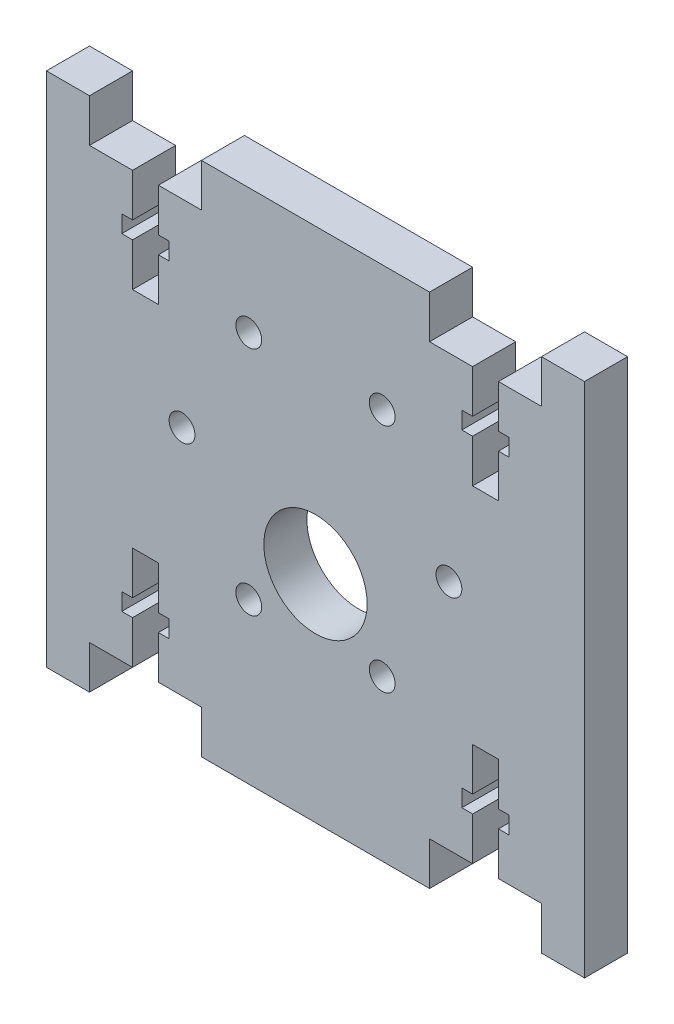
SolidWorks part; units mm, degrees
ref_plane "Front Plane" through (0, 0, 0) normal (0, 0, 1) x (1, 0, 0)
ref_plane "Top Plane" through (0, 0, 0) normal (0, 1, 0) x (1, 0, 0)
ref_plane "Right Plane" through (0, 0, 0) normal (1, 0, 0) x (0, 0, -1)
sketch "Sketch1" plane through (0, 0, 0) normal (0, 0, 1) x (1, 0, 0)
  line L1 (-27.5, -27) -> (27.5, -27)
  line L2 (-27.5, -27) -> (-27.5, 23)
  line L3 (-27.5, 23) -> (27.5, 23)
  line L4 (27.5, -27) -> (27.5, 23)
  line L5 (-27.5, -7) -> (27.5, -7) construction
  circle A2 centre (0, -7) radius 6
  circle A3 centre (0, 0) radius 15.5 construction
  circle A4 centre (-15.5, 0) radius 1.5
  circle A5 centre (-7.75, 13.4234) radius 1.5
  circle A6 centre (7.75, 13.4234) radius 1.5
  circle A7 centre (15.5, 0) radius 1.5
  circle A8 centre (7.75, -13.4234) radius 1.5
  circle A9 centre (-7.75, -13.4234) radius 1.5
  dimension "D1" = 12
  dimension "D5" = 3
  dimension "D8" = 31
  dimension "D2" = 55
  dimension "D3" = 50
  dimension "D6" = 20
  dimension "D7" = 7
  dimension "D4" = 6
extrude "Boss-Extrude1" add sketch "Sketch1" along normal blind 5
sketch "Sketch2" plane through (0, 0, 5) normal (0, 0, 1) x (1, 0, 0)
  line L0 (-27.5, -27) -> (27.5, -27) construction
  line L1 (-22.5, -20) -> (-17, -20)
  line L2 (-22.5, -20) -> (-22.5, -22)
  line L3 (-22.5, -22) -> (-17, -22)
  line L4 (-17, -20) -> (-17, -22)
  line L5 (-22.5, -20) -> (-17, -22) construction
  line L6 (-22.5, -22) -> (-17, -20) construction
  line L7 (17, -20) -> (22.5, -20)
  line L8 (17, -20) -> (17, -22)
  line L9 (17, -22) -> (22.5, -22)
  line L10 (22.5, -20) -> (22.5, -22)
  line L11 (17, -20) -> (22.5, -22) construction
  line L12 (17, -22) -> (22.5, -20) construction
  line L13 (-18.25, -15) -> (-21.25, -15)
  line L14 (-18.25, -15) -> (-18.25, -27)
  line L15 (-18.25, -27) -> (-21.25, -27)
  line L16 (-21.25, -15) -> (-21.25, -27)
  line L17 (-18.25, -15) -> (-21.25, -27) construction
  line L18 (-18.25, -27) -> (-21.25, -15) construction
  line L19 (-27.5, -2) -> (27.5, -2) construction
  line L20 (21.25, -15) -> (18.25, -15)
  line L21 (21.25, -15) -> (21.25, -27)
  line L22 (21.25, -27) -> (18.25, -27)
  line L23 (18.25, -15) -> (18.25, -27)
  line L24 (21.25, -15) -> (18.25, -27) construction
  line L25 (21.25, -27) -> (18.25, -15) construction
  line L26 (-27.5, 23) -> (-27.5, -27) construction
  line L27 (27.5, -27) -> (27.5, 23) construction
  line L28 (21.25, 23) -> (18.25, 11) construction
  line L29 (21.25, 11) -> (18.25, 23) construction
  line L30 (-18.25, 23) -> (-21.25, 11) construction
  line L31 (-18.25, 11) -> (-21.25, 23) construction
  line L32 (17, 18) -> (22.5, 16) construction
  line L33 (17, 16) -> (22.5, 18) construction
  line L34 (-22.5, 18) -> (-17, 16) construction
  line L35 (-22.5, 16) -> (-17, 18) construction
  line L36 (18.25, 11) -> (18.25, 23)
  line L37 (21.25, 23) -> (18.25, 23)
  line L38 (21.25, 11) -> (21.25, 23)
  line L39 (21.25, 11) -> (18.25, 11)
  line L40 (-21.25, 11) -> (-21.25, 23)
  line L41 (-18.25, 23) -> (-21.25, 23)
  line L42 (-18.25, 11) -> (-18.25, 23)
  line L43 (-18.25, 11) -> (-21.25, 11)
  line L44 (22.5, 16) -> (22.5, 18)
  line L45 (17, 18) -> (22.5, 18)
  line L46 (17, 16) -> (17, 18)
  line L47 (17, 16) -> (22.5, 16)
  line L48 (-17, 16) -> (-17, 18)
  line L49 (-22.5, 18) -> (-17, 18)
  line L50 (-22.5, 16) -> (-22.5, 18)
  line L51 (-22.5, 16) -> (-17, 16)
  point P0 (-19.75, -21)
  point P5 (19.75, -21)
  point P10 (-19.75, -21)
  point P17 (19.75, -21)
  point P44 (19.75, 17)
  point P45 (-19.75, 17)
  dimension "D1" = 5.5
  dimension "D2" = 2
  dimension "D3" = 5.5
  dimension "D4" = 2
  dimension "D5" = 3
  dimension "D6" = 3
  dimension "D7" = 12
  dimension "D8" = 12
  dimension "D9" = 5
  dimension "D10" = 5
extrude "Cut-Extrude1" cut sketch "Sketch2" against normal blind 5 contours L43 L40 L41 L42 | L48 L49 L50 L51 | L36 L37 L38 L39 | L46 L45 L44 L47 | L14 L15 L16 L13 | L4 L3 L2 L1 | L23 L22 L21 L20 | L8 L9 L10 L7
sketch "Sketch3" plane through (0, 0, 5) normal (0, 0, 1) x (1, 0, 0)
  line L0 (-18.25, -27) -> (18.25, -27) construction
  line L1 (-13.25, -27) -> (13.25, -27)
  line L2 (-13.25, -27) -> (-13.25, -32)
  line L3 (-13.25, -32) -> (13.25, -32)
  line L4 (13.25, -27) -> (13.25, -32)
  line L5 (-26.25, -29.5) -> (-13.25, -29.5) construction
  line L6 (-21.25, -22) -> (-21.25, -27) construction
  line L7 (21.25, -22) -> (21.25, -27) construction
  line L8 (26.25, -32) -> (31.25, -32)
  line L9 (26.25, -32) -> (26.25, 28)
  line L12 (27.5, -32) -> (26.25, -32)
  line L13 (26.25, -23.7445) -> (26.25, -32)
  line L14 (-19.75, -29.5) -> (-19.75, -15) construction
  line L15 (-18.25, -15) -> (-21.25, -15) construction
  line L16 (26.25, 28) -> (31.25, 28)
  line L17 (-21.25, 23) -> (-27.5, 23) construction
  line L18 (-26.25, -32) -> (-31.25, -32)
  line L19 (-26.25, -32) -> (-26.25, 28)
  line L20 (-26.25, 28) -> (-31.25, 28)
  line L21 (-31.25, -32) -> (-31.25, 28)
  line L22 (31.25, -32) -> (31.25, 28)
  line L23 (-27.5, -27) -> (-21.25, -27) construction
  line L24 (26.25, -29.5) -> (13.25, -29.5) construction
  line L25 (19.75, -29.5) -> (19.75, -15) construction
  line L26 (21.25, -15) -> (18.25, -15) construction
  line L27 (-26.25, -2) -> (26.25, -2) construction
  line L28 (13.25, 23) -> (13.25, 28)
  line L29 (-13.25, 28) -> (13.25, 28)
  line L30 (-13.25, 23) -> (-13.25, 28)
  line L31 (-13.25, 23) -> (13.25, 23)
  point P30 (-24.375, -27)
  dimension "D1" = 5
  dimension "D2" = 5
  dimension "D3" = 5
  dimension "D4" = 5
  dimension "D5" = 5
  dimension "D6" = 5
extrude "Boss-Extrude2" add sketch "Sketch3" against normal blind 5 contours L21 L18 L19 L20 | L4 L1 L2 L3 | L8 L22 L16 L9 | L30 L31 L28 L29 region at (0, -29.5, 5) region at (28.75, -2, 5) region at (-28.75, -2, 5) region at (0, 25.5, 5)
